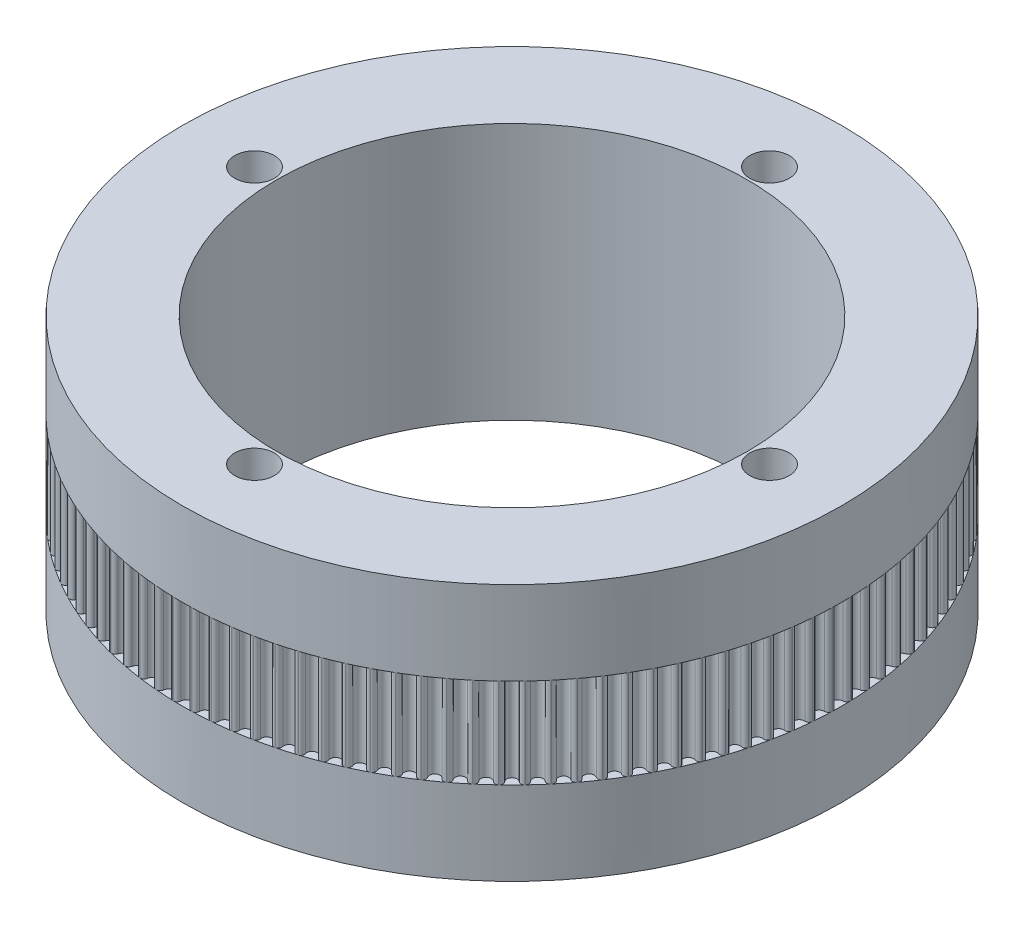
SolidWorks part; units mm, degrees
ref_plane "Front plan" through (0, 0, 0) normal (0, 0, 1) x (1, 0, 0)
ref_plane "Top plan" through (0, 0, 0) normal (0, 1, 0) x (1, 0, 0)
ref_plane "Right plan" through (0, 0, 0) normal (1, 0, 0) x (0, 0, -1)
sketch "Skica2" plane through (0, 0, 0) normal (0, 0, 1) x (1, 0, 0)
  line L1 (25, 4.775) -> (25, -4.775)
  line L3 (0, -9) -> (0, 9) construction
  line L7 (36, 3.775) -> (35, 3.775)
  line L8 (35, 3.775) -> (35, -3.775)
  line L9 (36, 3.775) -> (36, 4.775)
  line L12 (36, -4.775) -> (25.7839, -4.775)
  line L13 (36, 4.775) -> (25.489, 4.775)
  line L14 (36, -4.775) -> (36, -3.775)
  line L15 (35, -3.775) -> (36, -3.775)
  line L17 (25.489, 4.775) -> (25, 4.775)
  line L18 (25.7839, -4.775) -> (25, -4.775)
  point P0 (25.7839, -4.775)
  point P3 (25, 0)
  point P7 (0, 0)
  dimension "D3" = 70
  dimension "D1" = 50
  dimension "D2" = 9.55
  dimension "D4" = 1
  dimension "D5" = 1
revolve "Revolute" add sketch "Skica2" angle 360 about L3
sketch "Sketch2" plane through (0, 3.775, 0) normal (0, -1, 0) x (1, 0, 0)
  line L0 (0, 0) -> (0, 34.6075) construction
  line L1 (0, 0) -> (11.8019, 32.9502) construction
  line L3 (0, 0) -> (-2.5216, 34.909) construction
  circle A1 centre (0, 0) radius 34.0575 construction
  circle A2 centre (0, 0) radius 34.6 construction
  arc A3 (-0.5499, 34.5956) -> (0.5499, 34.5956) centre (0, 34.6075) ccw
  arc A7 (-0.9608, 34.9868) -> (-2.5216, 34.909) centre (0, 0) ccw
  arc A8 (0, 36.241) -> (2.5216, 34.909) centre (0.9503, 34.9871) cw
  circle A9 centre (0, 0) radius 35 construction
  arc A10 (0.9608, 34.9868) -> (2.5216, 34.909) centre (0, 0) cw
  arc A11 (0.9608, 34.9868) -> (0.5499, 34.5956) centre (0.9498, 34.587) ccw
  arc A12 (0, 36.241) -> (-2.5216, 34.909) centre (-0.9503, 34.9871) ccw
  arc A13 (-0.9608, 34.9868) -> (-0.5499, 34.5956) centre (-0.9498, 34.587) cw
  dimension "D2" = 0.8
  dimension "D4" = 0.55
  dimension "D6" = 70
  dimension "D3" = 1.5733
  dimension "D1" = 0.4
extrude "Cut-Extrude3" cut sketch "Sketch2" along normal mid plane 50
pattern_circular "CirPattern1" count 112 over 360 about axis through (0, 0, 0) along (0, 1, 0) of "Cut-Extrude3"
sketch "Sketch4" plane through (0, -4.775, 0) normal (0, -1, 0) x (1, 0, 0)
  circle A0 centre (0, 0) radius 20.125
  circle A1 centre (0, 0) radius 7.25
  dimension "D1" = 40.25
  dimension "D2" = 14.5
extrude "Cut-Extrude4" [suppressed] cut sketch "Sketch4" against normal blind 2
ref_plane "Plane1" through (0, 1.575, 0) normal (0, -1, 0) x (-1, 0, 0)
mirror "Mirror1" [suppressed] about plane through (0, 0, 0) normal (0, 1, 0)
sketch "Sketch7" plane through (0, -4.775, 0) normal (0, -1, 0) x (1, 0, 0)
  circle A0 centre (-27.35, 0) radius 2.1
  dimension "D1" = 27.35
  dimension "D2" = 4.2
extrude "Cut-Extrude5" cut sketch "Sketch7" against normal through all
pattern_circular "CirPattern2" count 4 over 270 about axis through (0, 0, 0) along (0, 1, 0) of "Cut-Extrude5"
sketch "Sketch8" plane through (0, -4.775, 0) normal (0, -1, 0) x (1, 0, 0)
  circle A0 centre (0, 0) radius 35
  circle A1 centre (-27.35, 0) radius 2.1
  circle A2 centre (0, 27.35) radius 2.1
  circle A3 centre (27.35, 0) radius 2.1
  circle A4 centre (0, -27.35) radius 2.1
  circle A6 centre (0, 0) radius 25
  circle A8 centre (0, 0) radius 25 construction
  circle A9 centre (-27.35, 0) radius 2.1 construction
  circle A10 centre (0, -27.35) radius 2.1 construction
extrude "Boss-Extrude1" add sketch "Sketch8" along normal blind 8.875
mirror "Mirror2" about plane through (0, 0, 0) normal (0, 1, 0) of "Boss-Extrude1"
sketch "Sketch9" plane through (0, 13.65, 0) normal (0, 1, 0) x (1, 0, 0)
  circle A0 centre (0, 0) radius 10.25
  dimension "D1" = 20.5
equation "\"`\"=2"
equation "\"D6@Sketch2\"= \"D3@Skica2\""
